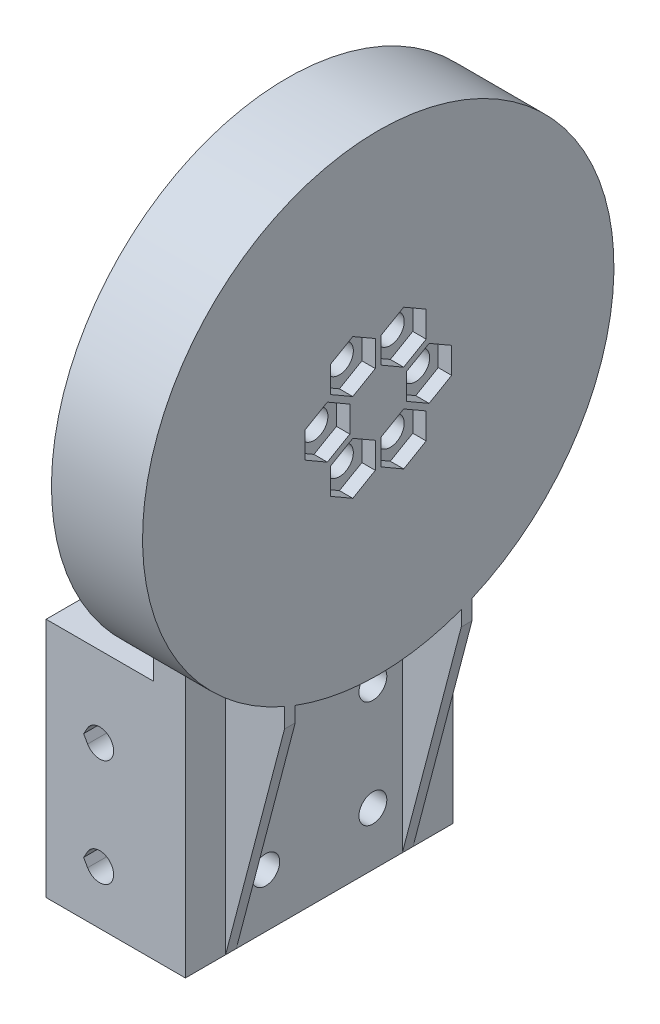
SolidWorks part; units mm, degrees
ref_plane "Front Plane" through (0, 0, 0) normal (0, 0, 1) x (1, 0, 0)
ref_plane "Top Plane" through (0, 0, 0) normal (0, 1, 0) x (1, 0, 0)
ref_plane "Right Plane" through (0, 0, 0) normal (1, 0, 0) x (0, 0, -1)
sketch "Sketch1" plane through (0, 0, 0) normal (1, 0, 0) x (0, 0, -1)
  line L0 (0, 0) -> (4.75, 8.2272) construction
  line L1 (0, -21.4441) -> (0, 21.4441) construction
  circle A0 centre (0, 0) radius 9.5 construction
  circle A7 centre (0, 0) radius 22.5
  circle A8 centre (0, 0) radius 30
  circle A9 centre (0, 0) radius 44
  circle A10 centre (4.75, 8.2272) radius 2.6
  circle A11 centre (9.5, 0) radius 2.6
  circle A12 centre (4.75, -8.2272) radius 2.6
  circle A13 centre (-4.75, -8.2272) radius 2.6
  circle A14 centre (-9.5, 0) radius 2.6
  circle A15 centre (-4.75, 8.2272) radius 2.6
  point P18 (0, 0)
  point P22 (0, 0)
  dimension "D1" = 19
  dimension "D2" = 5.2
  dimension "D4" = 60
  dimension "D5" = 45
  dimension "D6" = 88
  dimension "D7" = 30
  dimension "D3" = 6
extrude "Boss-Extrude1" add sketch "Sketch1" along normal blind 5 contours A7 A11 A12 A13 A14 | A8 A7 | A9 A8 region at (0, 0, 0) region at (0, 0, 29.1515) region at (0, 0, 42.7555)
extrude "Boss-Extrude2" add sketch "Sketch1<3>" against normal blind 4.5 contours A9 | A7
sketch "Sketch1<3>" plane through (0, 0, 0) normal (1, 0, 0) x (0, 0, -1) same geometry as "Sketch1"
sketch "Sketch2" plane through (-4.5, 0, 0) normal (-1, 0, 0) x (0, 0, 1)
  circle A0 centre (0, 0) radius 37.7
  circle A1 centre (0, 0) radius 44
  dimension "D1" = 75.4
  dimension "D2" = 88
extrude "Boss-Extrude3" add sketch "Sketch2" along normal blind 7.5
sketch "Sketch3" plane through (-12, 0, 0) normal (-1, 0, 0) x (0, 0, 1)
  line L0 (0, 0) -> (0, -82.3798) construction
  line L1 (25, -44) -> (-25, -44) construction
  line L2 (-25, -86) -> (25, -86)
  line L3 (-25, -86) -> (-25, -36.2077)
  line L5 (25, -86) -> (25, -36.2077)
  circle A0 centre (0, 0) radius 44 construction
  circle A2 centre (0, 0) radius 44
  arc A3 (-25, -36.2077) -> (25, -36.2077) centre (0, 0) ccw
  point P12 (0, -44)
  dimension "D1" = 50
  dimension "D2" = 25
  dimension "D3" = 42
  dimension "D4" = 0
extrude "Boss-Extrude4" add sketch "Sketch3" against normal blind 6
sketch "Sketch4" plane through (-4.5, 0, 0) normal (-1, 0, 0) x (0, 0, 1)
  circle A0 centre (0, 0) radius 35.25
  dimension "D1" = 70.5
extrude "Cut-Extrude1" cut sketch "Sketch4" against normal blind 1
sketch "Sketch5" plane through (-12, 0, 0) normal (-1, 0, 0) x (0, 0, 1)
  line L0 (-25, -36.2077) -> (-25, -86) construction
  line L1 (-25, -46) -> (25, -46)
  line L2 (-25, -46) -> (-25, -41)
  line L3 (-25, -41) -> (25, -41)
  line L4 (25, -46) -> (25, -41)
  line L5 (25, -86) -> (25, -36.2077) construction
  line L6 (-25, -86) -> (25, -86) construction
  line L8 (-20, -46) -> (-25, -46)
  line L9 (-20, -46) -> (-20, -86)
  line L10 (-20, -86) -> (-25, -86)
  line L11 (-25, -46) -> (-25, -86)
  line L12 (20, -46) -> (25, -46)
  line L13 (20, -46) -> (20, -86)
  line L14 (20, -86) -> (25, -86)
  line L15 (25, -46) -> (25, -86)
  line M4 (-25, -36.2077) -> (-25, -86)
  line M5 (-25, -86) -> (25, -86)
  line M6 (25, -86) -> (25, -36.2077)
  dimension "D1" = 5
  dimension "D2" = 40
  dimension "D3" = 5
  dimension "D4" = 5
extrude "Boss-Extrude5" add sketch "Sketch5" along normal blind 20 contours L9 L1 M4 M5 | L3 L1 M4 M6 | L1 L13 M5 M6 region at (-12, -43.5, 0) region at (-12, -66, -22.5) region at (-12, -66, 22.5)
ref_plane "Plane1" through (0, 0, 16.5) normal (0, 0, 1) x (1, 0, 0)
ref_plane "Plane2" through (0, 0, -16.5) normal (0, 0, -1) x (-1, 0, 0)
sketch "Sketch6" plane through (0, 0, 16.5) normal (0, 0, 1) x (1, 0, 0)
  line L1 (5, -44) -> (5, 44) construction
  line L2 (5, -40) -> (-6, -40)
  line L3 (-6, -44) -> (-6, -36.2077) construction
  line L4 (-6, -40) -> (-6, -86)
  line L5 (5, -40) -> (5, -44)
  line L6 (5, -44) -> (-6, -86)
  dimension "D1" = 46
extrude "Boss-Extrude7" add sketch "Sketch6" along normal blind 1 and the other way blind 1
sketch "Sketch7" plane through (0, 0, -16.5) normal (0, 0, -1) x (-1, 0, 0)
  line L1 (-5, 44) -> (-5, -44) construction
  line L2 (-5, -40) -> (6, -40)
  line L3 (6, -36.2077) -> (6, -40.3702) construction
  line L4 (6, -40) -> (6, -86)
  line L5 (-5, -40) -> (-5, -44)
  line L6 (-5, -44) -> (6, -86)
  dimension "D1" = 46
extrude "Boss-Extrude8" add sketch "Sketch7" along normal blind 1 and the other way blind 1
sketch "Sketch8" plane through (-6, 0, 0) normal (1, 0, 0) x (0, 0, -1)
  line L0 (-10, -86) -> (-10, -34.0161) construction
  line L1 (15.5, -86) -> (-15.5, -86) construction
  line L2 (10, -86) -> (10, -33.8504) construction
  line L3 (-25, -86) -> (-25, -36.2077) construction
  line L4 (25, -36.2077) -> (25, -86) construction
  line L5 (-10, -56) -> (10, -56) construction
  line L6 (-10, -76) -> (10, -76) construction
  circle A0 centre (-10, -76) radius 2.6
  circle A1 centre (10, -76) radius 2.6
  circle A2 centre (-10, -56) radius 2.6
  circle A3 centre (10, -56) radius 2.6
  dimension "D5" = 5.2
  dimension "D6" = 5.2
  dimension "D7" = 5.2
  dimension "D8" = 5.2
  dimension "D1" = 15
  dimension "D2" = 15
  dimension "D3" = 10
  dimension "D4" = 20
extrude "Cut-Extrude2" cut sketch "Sketch8" against normal through all
sketch "Sketch9" plane through (0, 0, 25) normal (0, 0, 1) x (1, 0, 0)
  line L0 (-6, -86) -> (-32, -86) construction
  line L1 (-32, -86) -> (-32, -41) construction
  line L2 (-22, -76) -> (-22, -56) construction
  line L3 (-22, -56) -> (-32, -56) construction
  line L4 (-32, -41) -> (-32, -86) construction
  line L5 (-22, -76) -> (-32, -76) construction
  line L6 (-24.2533, -54.7029) -> (-25, -56)
  line L7 (-25, -56) -> (-24.2533, -57.2971)
  line L8 (-24.2533, -74.7029) -> (-25, -76)
  line L9 (-25, -76) -> (-24.2533, -77.2971)
  circle A0 centre (-22, -76) radius 2.6
  circle A1 centre (-22, -56) radius 2.6
  dimension "D3" = 5.2
  dimension "D4" = 5.2
  dimension "D1" = 10
  dimension "D2" = 20
  dimension "D5" = 10
  dimension "D6" = 3
  dimension "D7" = 3
extrude "Cut-Extrude3" cut sketch "Sketch9" against normal through all contours A1 | A1 L6 L7 | A0 | A0 L8 L9 region at (-24.6867, -56, 25) region at (-22, -56, 25) region at (-24.6867, -76, 25) region at (-22, -76, 25)
sketch "Sketch10" plane through (5, 0, 0) normal (1, 0, 0) x (0, 0, -1)
  line L0 (9.5, -4.8497) -> (13.7, -2.4249)
  line L1 (8.95, 5.8024) -> (8.95, 10.6521)
  line L2 (8.95, 10.6521) -> (4.75, 13.077)
  line L3 (4.75, 13.077) -> (0.55, 10.6521)
  line L4 (0.55, 10.6521) -> (0.55, 5.8024)
  line L5 (0.55, 5.8024) -> (4.75, 3.3775)
  line L6 (4.75, 3.3775) -> (8.95, 5.8024)
  line L7 (13.7, -2.4249) -> (13.7, 2.4249)
  line L8 (13.7, 2.4249) -> (9.5, 4.8497)
  line L9 (9.5, 4.8497) -> (5.3, 2.4249)
  line L10 (5.3, 2.4249) -> (5.3, -2.4249)
  line L11 (5.3, -2.4249) -> (9.5, -4.8497)
  line L12 (0.55, -10.6521) -> (4.75, -13.077)
  line L13 (4.75, -13.077) -> (8.95, -10.6521)
  line L14 (8.95, -10.6521) -> (8.95, -5.8024)
  line L15 (8.95, -5.8024) -> (4.75, -3.3775)
  line L16 (4.75, -3.3775) -> (0.55, -5.8024)
  line L17 (0.55, -5.8024) -> (0.55, -10.6521)
  line L18 (-8.95, -5.8024) -> (-8.95, -10.6521)
  line L19 (-8.95, -10.6521) -> (-4.75, -13.077)
  line L20 (-4.75, -13.077) -> (-0.55, -10.6521)
  line L21 (-0.55, -10.6521) -> (-0.55, -5.8024)
  line L22 (-0.55, -5.8024) -> (-4.75, -3.3775)
  line L23 (-4.75, -3.3775) -> (-8.95, -5.8024)
  line L24 (-9.5, 4.8497) -> (-13.7, 2.4249)
  line L25 (-13.7, 2.4249) -> (-13.7, -2.4249)
  line L26 (-13.7, -2.4249) -> (-9.5, -4.8497)
  line L27 (-9.5, -4.8497) -> (-5.3, -2.4249)
  line L28 (-5.3, -2.4249) -> (-5.3, 2.4249)
  line L29 (-5.3, 2.4249) -> (-9.5, 4.8497)
  line L30 (-0.55, 10.6521) -> (-4.75, 13.077)
  line L31 (-4.75, 13.077) -> (-8.95, 10.6521)
  line L32 (-8.95, 10.6521) -> (-8.95, 5.8024)
  line L33 (-8.95, 5.8024) -> (-4.75, 3.3775)
  line L34 (-4.75, 3.3775) -> (-0.55, 5.8024)
  line L35 (-0.55, 5.8024) -> (-0.55, 10.6521)
  line L36 (0, -17.4605) -> (0, 17.4605) construction
  line L37 (0, 0) -> (4.75, 8.2272) construction
  circle A0 centre (4.75, 8.2272) radius 4.2 construction
  point P10 (2.65, 4.5899)
  point P44 (0, 0)
  dimension "D4" = 9.5
  dimension "D3" = 30
  dimension "D1" = 8.4
  dimension "D2" = 6
extrude "Cut-Extrude4" cut sketch "Sketch10" against normal blind 2.5
sketch "Sketch11" plane through (5, 0, 0) normal (1, 0, 0) x (0, 0, -1)
  line L0 (-4.75, 8.2272) -> (-4.75, 11.277) construction
  line L1 (12.75, 1.8764) -> (9.5, 3.7528)
  line L2 (4.75, 11.98) -> (1.5, 10.1036)
  line L3 (1.5, 10.1036) -> (1.5, 6.3509)
  line L4 (1.5, 6.3509) -> (4.75, 4.4745)
  line L5 (4.75, 4.4745) -> (8, 6.3509)
  line L6 (8, 6.3509) -> (8, 10.1036)
  line L7 (8, 10.1036) -> (4.75, 11.98)
  line L8 (9.5, 3.7528) -> (6.25, 1.8764)
  line L9 (6.25, 1.8764) -> (6.25, -1.8764)
  line L10 (6.25, -1.8764) -> (9.5, -3.7528)
  line L11 (9.5, -3.7528) -> (12.75, -1.8764)
  line L12 (12.75, -1.8764) -> (12.75, 1.8764)
  line L13 (8, -10.1036) -> (8, -6.3509)
  line L14 (8, -6.3509) -> (4.75, -4.4745)
  line L15 (4.75, -4.4745) -> (1.5, -6.3509)
  line L16 (1.5, -6.3509) -> (1.5, -10.1036)
  line L17 (1.5, -10.1036) -> (4.75, -11.98)
  line L18 (4.75, -11.98) -> (8, -10.1036)
  line L19 (-4.75, -11.98) -> (-1.5, -10.1036)
  line L20 (-1.5, -10.1036) -> (-1.5, -6.3509)
  line L21 (-1.5, -6.3509) -> (-4.75, -4.4745)
  line L22 (-4.75, -4.4745) -> (-8, -6.3509)
  line L23 (-8, -6.3509) -> (-8, -10.1036)
  line L24 (-8, -10.1036) -> (-4.75, -11.98)
  line L25 (-12.75, -1.8764) -> (-9.5, -3.7528)
  line L26 (-9.5, -3.7528) -> (-6.25, -1.8764)
  line L27 (-6.25, -1.8764) -> (-6.25, 1.8764)
  line L28 (-6.25, 1.8764) -> (-9.5, 3.7528)
  line L29 (-9.5, 3.7528) -> (-12.75, 1.8764)
  line L30 (-12.75, 1.8764) -> (-12.75, -1.8764)
  line L31 (-8, 10.1036) -> (-8, 6.3509)
  line L32 (-8, 6.3509) -> (-4.75, 4.4745)
  line L33 (-4.75, 4.4745) -> (-1.5, 6.3509)
  line L34 (-1.5, 6.3509) -> (-1.5, 10.1036)
  line L35 (-1.5, 10.1036) -> (-4.75, 11.98)
  line L36 (-4.75, 11.98) -> (-8, 10.1036)
  circle A0 centre (-4.75, 8.2272) radius 2.4 construction
  arc A1 (-3.8941, 11.5553) -> (-5.6059, 11.5553) centre (-4.75, 11.277) ccw construction
  arc A7 (-1.5398, 9.2078) -> (-2.3957, 10.6902) centre (-2.2088, 9.8098) ccw construction
  arc A8 (-2.3957, 5.9952) -> (-1.5398, 7.4776) centre (-2.2088, 6.8756) ccw construction
  arc A9 (-5.6059, 5.1301) -> (-3.8941, 5.1301) centre (-4.75, 5.4084) ccw construction
  arc A10 (-7.9602, 7.4776) -> (-7.1043, 5.9952) centre (-7.2912, 6.8756) ccw construction
  arc A11 (-7.1043, 10.6902) -> (-7.9602, 9.2078) centre (-7.2912, 9.8098) ccw construction
  arc A12 (-3.8941, 11.5553) -> (-2.3957, 10.6902) centre (-2.6642, 11.9554) ccw construction
  arc A13 (-1.5398, 9.2078) -> (-1.5398, 7.4776) centre (-0.5785, 8.3427) ccw construction
  arc A14 (-2.3957, 5.9952) -> (-3.8941, 5.1301) centre (-2.6642, 4.7301) ccw construction
  arc A15 (-5.6059, 5.1301) -> (-7.1043, 5.9952) centre (-6.8358, 4.7301) ccw construction
  arc A16 (-7.9602, 7.4776) -> (-7.9602, 9.2078) centre (-8.9215, 8.3427) ccw construction
  arc A17 (-7.1043, 10.6902) -> (-5.6059, 11.5553) centre (-6.8358, 11.9554) ccw construction
  arc A18 (2.4957, 10.6325) -> (1.6398, 9.1501) centre (2.3088, 9.7521) ccw construction
  arc A19 (1.6398, 7.4199) -> (1.6398, 9.1501) centre (0.6785, 8.285) ccw construction
  arc A20 (1.6398, 7.4199) -> (2.4957, 5.9375) centre (2.3088, 6.8178) ccw construction
  arc A21 (3.9941, 5.0723) -> (2.4957, 5.9375) centre (2.7642, 4.6723) ccw construction
  arc A22 (3.9941, 5.0723) -> (5.7059, 5.0723) centre (4.85, 5.3507) ccw construction
  arc A23 (7.2043, 5.9375) -> (5.7059, 5.0723) centre (6.9358, 4.6723) ccw construction
  arc A24 (7.2043, 5.9375) -> (8.0602, 7.4199) centre (7.3912, 6.8178) ccw construction
  arc A25 (8.0602, 9.1501) -> (8.0602, 7.4199) centre (9.0215, 8.285) ccw construction
  arc A26 (8.0602, 9.1501) -> (7.2043, 10.6325) centre (7.3912, 9.7521) ccw construction
  arc A27 (5.7059, 11.4976) -> (7.2043, 10.6325) centre (6.9358, 11.8976) ccw construction
  arc A28 (5.7059, 11.4976) -> (3.9941, 11.4976) centre (4.85, 11.2192) ccw construction
  arc A29 (2.4957, 10.6325) -> (3.9941, 11.4976) centre (2.7642, 11.8976) ccw construction
  circle A30 centre (4.75, 8.2272) radius 2.4 construction
  arc A31 (10.4559, 3.1549) -> (8.7441, 3.1549) centre (9.6, 2.8765) ccw construction
  arc A32 (7.2457, 2.2898) -> (8.7441, 3.1549) centre (7.5142, 3.5549) ccw construction
  arc A33 (7.2457, 2.2898) -> (6.3898, 0.8074) centre (7.0588, 1.4094) ccw construction
  arc A34 (6.3898, -0.9228) -> (6.3898, 0.8074) centre (5.4285, -0.0577) ccw construction
  arc A35 (6.3898, -0.9228) -> (7.2457, -2.4053) centre (7.0588, -1.5249) ccw construction
  arc A36 (8.7441, -3.2704) -> (7.2457, -2.4053) centre (7.5142, -3.6704) ccw construction
  arc A37 (8.7441, -3.2704) -> (10.4559, -3.2704) centre (9.6, -2.992) ccw construction
  arc A38 (11.9543, -2.4053) -> (10.4559, -3.2704) centre (11.6858, -3.6704) ccw construction
  arc A39 (11.9543, -2.4053) -> (12.8102, -0.9228) centre (12.1412, -1.5249) ccw construction
  arc A40 (12.8102, 0.8074) -> (12.8102, -0.9228) centre (13.7715, -0.0577) ccw construction
  arc A41 (12.8102, 0.8074) -> (11.9543, 2.2898) centre (12.1412, 1.4094) ccw construction
  arc A42 (10.4559, 3.1549) -> (11.9543, 2.2898) centre (11.6858, 3.5549) ccw construction
  circle A43 centre (9.5, 0) radius 2.4 construction
  arc A44 (7.9602, -7.4776) -> (7.1043, -5.9952) centre (7.2912, -6.8756) ccw construction
  arc A45 (5.6059, -5.1301) -> (7.1043, -5.9952) centre (6.8358, -4.7301) ccw construction
  arc A46 (5.6059, -5.1301) -> (3.8941, -5.1301) centre (4.75, -5.4084) ccw construction
  arc A47 (2.3957, -5.9952) -> (3.8941, -5.1301) centre (2.6642, -4.7301) ccw construction
  arc A48 (2.3957, -5.9952) -> (1.5398, -7.4776) centre (2.2088, -6.8756) ccw construction
  arc A49 (1.5398, -9.2078) -> (1.5398, -7.4776) centre (0.5785, -8.3427) ccw construction
  arc A50 (1.5398, -9.2078) -> (2.3957, -10.6902) centre (2.2088, -9.8098) ccw construction
  arc A51 (3.8941, -11.5553) -> (2.3957, -10.6902) centre (2.6642, -11.9554) ccw construction
  arc A52 (3.8941, -11.5553) -> (5.6059, -11.5553) centre (4.75, -11.277) ccw construction
  arc A53 (7.1043, -10.6902) -> (5.6059, -11.5553) centre (6.8358, -11.9554) ccw construction
  arc A54 (7.1043, -10.6902) -> (7.9602, -9.2078) centre (7.2912, -9.8098) ccw construction
  arc A55 (7.9602, -7.4776) -> (7.9602, -9.2078) centre (8.9215, -8.3427) ccw construction
  circle A56 centre (4.75, -8.2272) radius 2.4 construction
  arc A57 (-2.4957, -10.6325) -> (-1.6398, -9.1501) centre (-2.3088, -9.7521) ccw construction
  arc A58 (-1.6398, -7.4199) -> (-1.6398, -9.1501) centre (-0.6785, -8.285) ccw construction
  arc A59 (-1.6398, -7.4199) -> (-2.4957, -5.9375) centre (-2.3088, -6.8178) ccw construction
  arc A60 (-3.9941, -5.0723) -> (-2.4957, -5.9375) centre (-2.7642, -4.6723) ccw construction
  arc A61 (-3.9941, -5.0723) -> (-5.7059, -5.0723) centre (-4.85, -5.3507) ccw construction
  arc A62 (-7.2043, -5.9375) -> (-5.7059, -5.0723) centre (-6.9358, -4.6723) ccw construction
  arc A63 (-7.2043, -5.9375) -> (-8.0602, -7.4199) centre (-7.3912, -6.8178) ccw construction
  arc A64 (-8.0602, -9.1501) -> (-8.0602, -7.4199) centre (-9.0215, -8.285) ccw construction
  arc A65 (-8.0602, -9.1501) -> (-7.2043, -10.6325) centre (-7.3912, -9.7521) ccw construction
  arc A66 (-5.7059, -11.4976) -> (-7.2043, -10.6325) centre (-6.9358, -11.8976) ccw construction
  arc A67 (-5.7059, -11.4976) -> (-3.9941, -11.4976) centre (-4.85, -11.2192) ccw construction
  arc A68 (-2.4957, -10.6325) -> (-3.9941, -11.4976) centre (-2.7642, -11.8976) ccw construction
  circle A69 centre (-4.75, -8.2272) radius 2.4 construction
  arc A70 (-10.4559, -3.1549) -> (-8.7441, -3.1549) centre (-9.6, -2.8765) ccw construction
  arc A71 (-7.2457, -2.2898) -> (-8.7441, -3.1549) centre (-7.5142, -3.5549) ccw construction
  arc A72 (-7.2457, -2.2898) -> (-6.3898, -0.8074) centre (-7.0588, -1.4094) ccw construction
  arc A73 (-6.3898, 0.9228) -> (-6.3898, -0.8074) centre (-5.4285, 0.0577) ccw construction
  arc A74 (-6.3898, 0.9228) -> (-7.2457, 2.4053) centre (-7.0588, 1.5249) ccw construction
  arc A75 (-8.7441, 3.2704) -> (-7.2457, 2.4053) centre (-7.5142, 3.6704) ccw construction
  arc A76 (-8.7441, 3.2704) -> (-10.4559, 3.2704) centre (-9.6, 2.992) ccw construction
  arc A77 (-11.9543, 2.4053) -> (-10.4559, 3.2704) centre (-11.6858, 3.6704) ccw construction
  arc A78 (-11.9543, 2.4053) -> (-12.8102, 0.9228) centre (-12.1412, 1.5249) ccw construction
  arc A79 (-12.8102, -0.8074) -> (-12.8102, 0.9228) centre (-13.7715, 0.0577) ccw construction
  arc A80 (-12.8102, -0.8074) -> (-11.9543, -2.2898) centre (-12.1412, -1.4094) ccw construction
  arc A81 (-10.4559, -3.1549) -> (-11.9543, -2.2898) centre (-11.6858, -3.5549) ccw construction
  circle A82 centre (-9.5, 0) radius 2.4 construction
  circle A83 centre (4.75, 8.2272) radius 3.25 construction
  dimension "D1" = 4.8
  dimension "D2" = 6
  dimension "D4" = 1.8
  dimension "D5" = 1.2933
  dimension "D3" = 1.8
  dimension "D8" = 6.5
  dimension "D6" = 6
  dimension "D7" = 6
  dimension "D9" = 6
extrude "Boss-Extrude9" [suppressed] add sketch "Sketch11" against normal blind 1.4 separate body
equation "\"D2@Sketch3\"=\"D1@Sketch3\"/2"
